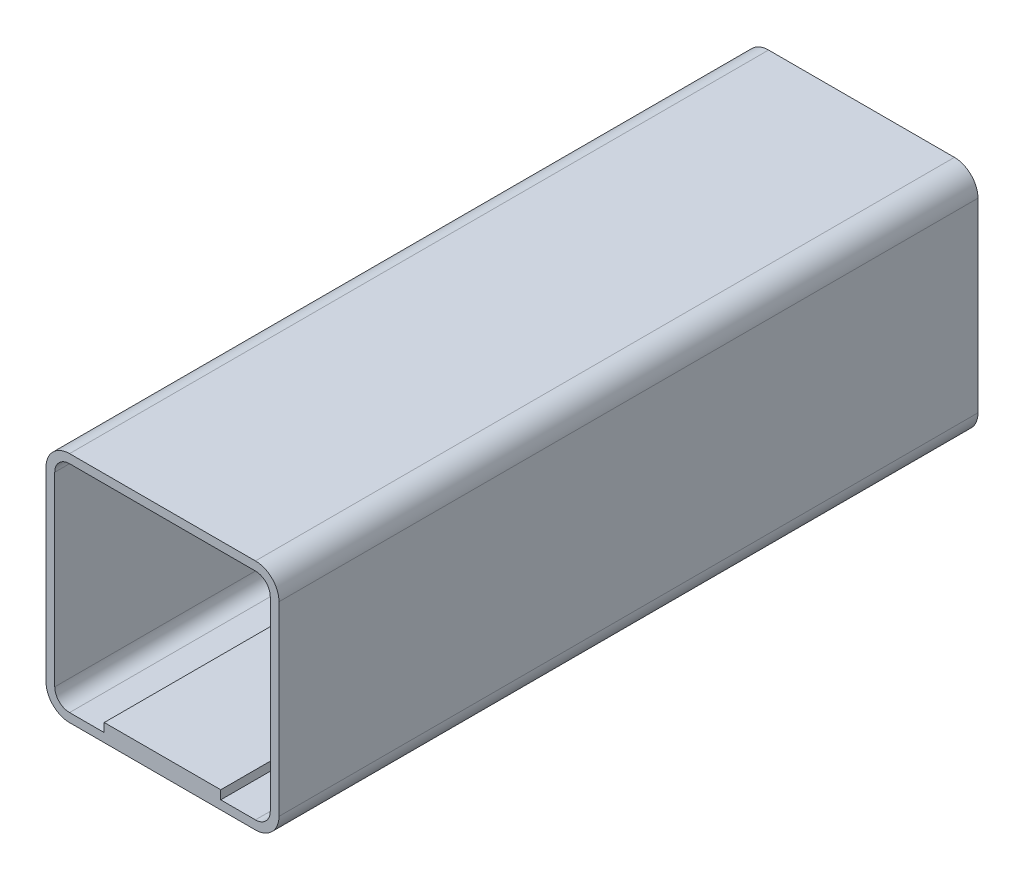
SolidWorks part; units mm, degrees
material "Polyurethane Foam Rigid"
ref_plane "Front Plane" through (0, 0, 0) normal (0, 0, 1) x (1, 0, 0)
ref_plane "Top Plane" through (0, 0, 0) normal (0, 1, 0) x (1, 0, 0)
ref_plane "Right Plane" through (0, 0, 0) normal (1, 0, 0) x (0, 0, -1)
sketch "Sketch1" plane through (0, 0, 0) normal (0, 0, 1) x (1, 0, 0)
  line L0 (-59.737, 59.737) -> (59.737, -59.737) construction
  line L1 (-50.6524, 63.5) -> (50.6524, 63.5)
  line L2 (-63.5, 50.6524) -> (-63.5, -50.6524)
  line L3 (-50.6524, -63.5) -> (50.6524, -63.5)
  line L4 (63.5, 50.6524) -> (63.5, -50.6524)
  arc A0 (63.5, 50.6524) -> (50.6524, 63.5) centre (50.6524, 50.6524) ccw
  arc A1 (50.6524, -63.5) -> (63.5, -50.6524) centre (50.6524, -50.6524) ccw
  arc A2 (-50.6524, -63.5) -> (-63.5, -50.6524) centre (-50.6524, -50.6524) cw
  arc A3 (-63.5, 50.6524) -> (-50.6524, 63.5) centre (-50.6524, 50.6524) cw
  point P0 (0, 0)
  point P1 (0, 0)
  point P18 (59.737, -59.737)
  dimension "D2" = 12.8476
  dimension "D3" = 12.8476
  dimension "D1" = 127
  dimension "D4" = 127
extrude "Boss-Extrude1" add sketch "Sketch1" against normal blind 381 contours L1 A0 L4 A1 L3 A2 L2 A3
shell "Shell1" thickness 4.7625 removed face at (0, 0, -381) removed face at (0, 0, 0)
sketch "Sketch3" plane through (0, 0, 0) normal (0, 0, 1) x (1, 0, 0)
  line L0 (-31.75, -58.7375) -> (31.75, -58.7375)
  line L1 (-50.6524, -58.7375) -> (50.6524, -58.7375) construction
  line L2 (0, -58.7375) -> (0, 0) construction
  line L3 (-31.75, -58.7375) -> (-31.75, -53.975)
  line L4 (-31.75, -53.975) -> (31.75, -53.975)
  line L5 (31.75, -53.975) -> (31.75, -58.7375)
  point P5 (0, -58.7375)
  dimension "D1" = 63.5
  dimension "D2" = 4.7625
extrude "Boss-Extrude2" add sketch "Sketch3" against normal up to surface (381 mm away) up to face at (0, 0, -381)
equation "\"span\"= 48"
equation "\"wing_chord\"= 9"
equation "\"fuse_len\"= 15"
equation "\"fuse_height\"= 5"
equation "\"fuse_wid\"= 5"
equation "\"D1@Boss-Extrude1\"= \"fuse_len\""
equation "\"D1@Sketch1\"= \"fuse_height\""
equation "\"D4@Sketch1\"= \"fuse_wid\""
equation "\"D1@Sketch3\"=\"fuse_wid\"/2"
equation "\"D2@Sketch3\"=3/16"
equation "\"foam_t\"= 0.1875"
equation "\"fuse_inner_arc_length\" = 0.5"
equation "\"fuse_inner_r\" = \"fuse_inner_arc_length\" * 4 / (2*pi)"
equation "\"fuse_outer_r\" = \"fuse_inner_r\" + \"foam_t\""
equation "\"main_spar_len\"= 36"
equation "\"x_fuse_to_wing\"= 3"
equation "\"x_cg_from_le\"= 2.25"
equation "\"boom_len\"= 30"
equation "\"wing_angle\"= 1.5"
equation "\"boom_d\"= 0.75"
equation "\"wing_spar_d\"= 0.375"
equation "\"wing_spar_l\"= 48"
equation "\"wing_spar_spacing\"= 1.35"
equation "\"wing_mount_l\"= 2.5"
equation "\"wing_mount_bolt_spacing\" = \"wing_mount_l\" * 0.5"
equation "\"boom_mount_l\"= 1"
equation "\"vstab_span\"= 6.5"
equation "\"hstab_span\"= 15.25"
equation "\"tail_chord\"= 5"
equation "\"D2@Sketch1\"= \"fuse_outer_r\""
equation "\"D3@Sketch1\"= \"fuse_outer_r\""
equation "\"fuse_inner_h\" = \"fuse_height\" - 2 * \"foam_t\""
equation "\"fuse_inner_w\" = \"fuse_wid\" - 2 * \"fuse_outer_r\""
